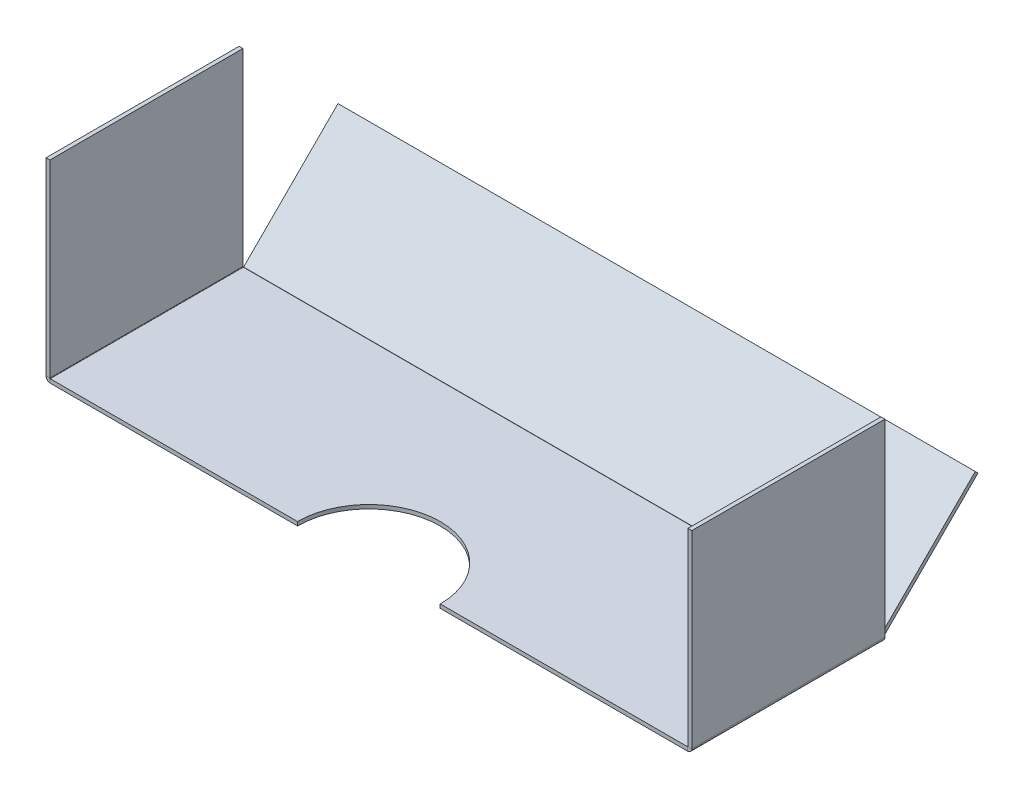
SolidWorks part; units mm, degrees
note: The reader was unsure of these and kept them because the rebuilt part matched: flange length of "边线-法兰1", "边线-法兰2".
ref_plane "前视基准面" through (0, 0, 0) normal (0, 0, 1) x (1, 0, 0)
ref_plane "上视基准面" through (0, 0, 0) normal (0, 1, 0) x (1, 0, 0)
ref_plane "右视基准面" through (0, 0, 0) normal (1, 0, 0) x (0, 0, -1)
sketch "草图1" plane through (0, 0, 0) normal (0, 1, 0) x (1, 0, 0)
  line L1 (-82.5, 25) -> (82.5, 25)
  line L2 (-82.5, 25) -> (-82.5, -25)
  line L3 (-82.5, -25) -> (82.5, -25)
  line L4 (82.5, 25) -> (82.5, -25)
  line L5 (0, -25) -> (0, 25) construction
  line L6 (-82.5, 0) -> (82.5, 0) construction
  point P0 (0, 0)
  dimension "D1" = 165
  dimension "D2" = 50
base flange "基体-法兰1" sketch "草图1" thickness 1 reverse thickness direction no parameters "D1"=0.1
edge flange "边线-法兰1" sketch "草图8" flange angle 90 flange length 50 flange position bend outside bend radius 0.1 thickness 1 parameters "D6"=10
sketch "草图8" plane through (-82.5, 0, 0) normal (-1, 0, 0) x (0, 0, 1)
  line L0 (-25, 0) -> (25, 0) construction
  line L1 (-25, 0) -> (25, 0)
  line L2 (-25, 0) -> (-25, 49)
  line L3 (-25, 49) -> (25, 49)
  line L4 (25, 49) -> (25, 0)
bend "边线折弯1" bend radius 0.1 bend angle 90 parameters "D5"=1
mirror "镜向1" about plane through (0, 0, 0) normal (1, 0, 0) of "边线-法兰1"
bend "镜向折弯1" bend radius 0.1 bend angle 90 parameters "D5"=2
sketch "草图9" plane through (0, 0, 0) normal (0, 1, 0) x (1, 0, 0)
  line L1 (-82.5, -25) -> (82.5, -25) construction
  circle A0 centre (0, -25) radius 18.4747
extrude "切除-拉伸1" cut sketch "草图9" against normal blind 10
edge flange "边线-法兰2" sketch "草图12" flange angle 135 flange length 35 flange position bend outside bend radius 0.1 thickness 1 parameters "D6"=10
sketch "草图12" plane through (0, 0, -25) normal (0, 0.7071, 0.7071) x (1, 0, 0)
  line L1 (82.5, 0) -> (-82.5, 0) construction
  line L2 (-82.5, 0) -> (-82.5, 34.5858)
  line L3 (-82.5, 34.5858) -> (82.5, 34.5858)
  line L4 (82.5, 34.5858) -> (82.5, 0)
  line L5 (82.5, 0) -> (-82.5, 0)
bend "边线折弯2" bend radius 0.1 bend angle 45 parameters "D5"=3
sketch "折弯-线1" [suppressed] plane through (0, 0, 0) normal (0, 1, 0) x (1, 0, 0)
sketch "边界框1" [suppressed] plane through (0, 0, 0) normal (0, 1, 0) x (1, 0, 0)
sheet metal parameters "钣金6" thickness 1 parameters "D1"=0.1
flat pattern "平板型式6" [suppressed]
sketch "折弯-线2" plane through (0, 0, 0) normal (0, 1, 0) x (1, 0, 0)
sketch "边界框2" [suppressed] plane through (0, 0, 0) normal (0, 1, 0) x (1, 0, 0)
sheet metal parameters "钣金7" thickness 1 parameters "D1"=0.1
flat pattern "平板型式6" [suppressed]
sketch "折弯-线2" plane through (0, 0, 0) normal (0, 1, 0) x (1, 0, 0)
sketch "边界框2" [suppressed] plane through (0, 0, 0) normal (0, 1, 0) x (1, 0, 0)
bend of the flat pattern "展开-<边线折弯1>1"
sheet metal parameters "钣金8" thickness 1 parameters "D1"=0.1
flat pattern "平板型式6" [suppressed]
sketch "折弯-线2" plane through (0, 0, 0) normal (0, 1, 0) x (1, 0, 0)
sketch "边界框2" [suppressed] plane through (0, 0, 0) normal (0, 1, 0) x (1, 0, 0)
bend of the flat pattern "展开-<边线折弯1>1"
bend of the flat pattern "展开-<镜向折弯1>1"
sheet metal parameters "钣金9" thickness 1 parameters "D1"=0.1
flat pattern "平板型式6" [suppressed]
sketch "折弯-线2" plane through (0, 0, 0) normal (0, 1, 0) x (1, 0, 0)
sketch "边界框2" [suppressed] plane through (0, 0, 0) normal (0, 1, 0) x (1, 0, 0)
bend of the flat pattern "展开-<边线折弯1>1"
bend of the flat pattern "展开-<镜向折弯1>1"
sheet metal parameters "钣金10" thickness 1 parameters "D1"=0.1
flat pattern "平板型式6"
sketch "折弯-线2" plane through (0, 0, 0) normal (0, 1, 0) x (1, 0, 0)
  line L0 (82.5, 25.2356) -> (-82.5, 25.2356) construction
  line L1 (82.9712, -25) -> (82.9712, 25) construction
  line L2 (-82.9712, 25) -> (-82.9712, -25) construction
  line L3 (82.5, 25.2356) -> (-82.5, 25.2356) construction
  line L4 (82.9712, -25) -> (82.9712, 25) construction
  line L5 (-82.9712, 25) -> (-82.9712, -25) construction
sketch3d "边界框2" [suppressed]
  line L0 (132.3425, -25, 0) -> (-132.3425, -25, 0) construction
  line L1 (132.3425, 60.0156, 0) -> (-132.3425, 60.0156, 0) construction
  line L2 (132.3425, -25, 0) -> (132.3425, 60.0156, 0) construction
  line L3 (-132.3425, -25, 0) -> (-132.3425, 60.0156, 0) construction
bend of the flat pattern "展开-<边线折弯1>1"
bend of the flat pattern "展开-<镜向折弯1>1"
bend of the flat pattern "展开-<边线折弯2>1"
